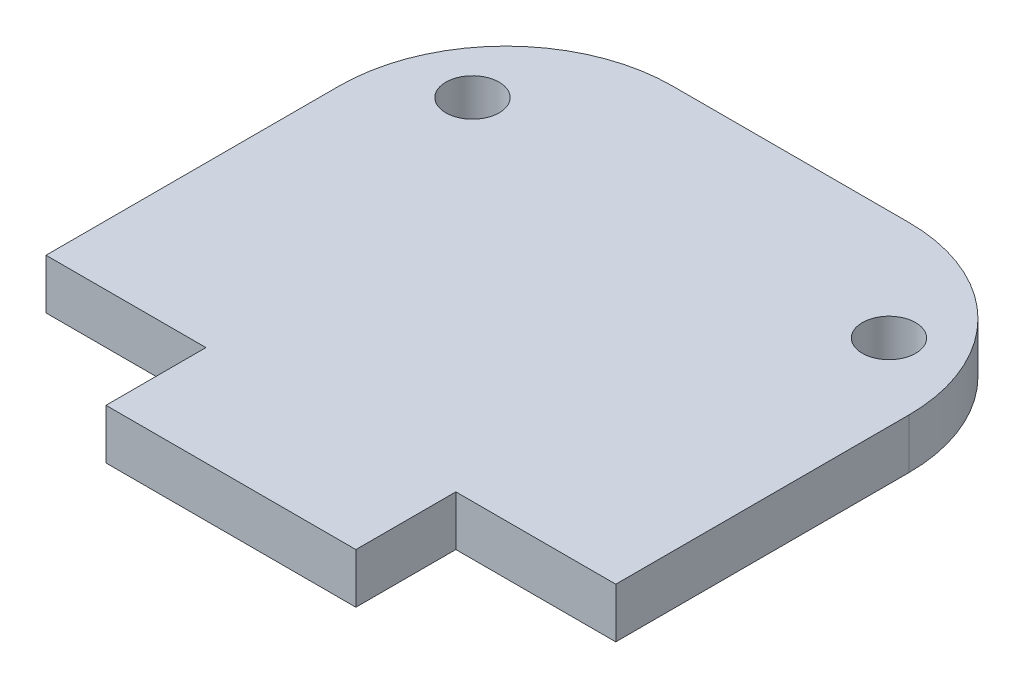
SolidWorks part; units mm, degrees
material "MDF"
ref_plane "Plano frontal" through (0, 0, 0) normal (0, 0, 1) x (1, 0, 0)
ref_plane "Plano superior" through (0, 0, 0) normal (0, 1, 0) x (1, 0, 0)
ref_plane "Plano direito" through (0, 0, 0) normal (1, 0, 0) x (0, 0, -1)
ref_plane "Plano1" through (0, -3, 0) normal (0, -1, 0) x (1, 0, 0)
sketch "Esboço1" plane through (0, -3, 0) normal (0, -1, 0) x (1, 0, 0)
  line L0 (-7.1, -33.6) -> (7.1, -33.6)
  line L1 (17.1, -23.6) -> (17.1, -6)
  line L2 (17.1, -6) -> (7.5, -6)
  line L3 (7.5, -6) -> (7.5, 0)
  line L4 (7.5, 0) -> (-7.5, 0)
  line L5 (-7.5, 0) -> (-7.5, -6)
  line L6 (-7.5, -6) -> (-17.1, -6)
  line L7 (-17.1, -6) -> (-17.1, -23.6)
  line L8 (-12.5, -27) -> (12.5, -27) construction
  line L9 (-7.5, -6) -> (7.5, -6) construction
  arc A0 (7.1, -33.6) -> (17.1, -23.6) centre (7.1, -23.6) ccw
  arc A1 (-17.1, -23.6) -> (-7.1, -33.6) centre (-7.1, -23.6) ccw
  circle A2 centre (-12.5, -27) radius 1.6
  circle A3 centre (12.5, -27) radius 1.6
  point P16 (0, 0)
  point P17 (0, -27)
  point P18 (0, -6)
  dimension "D1" = 25
  dimension "D2" = 3.2
  dimension "D6" = 10
  dimension "D3" = 15
  dimension "D4" = 6
  dimension "D5" = 21
  dimension "D7" = 6.6
  dimension "D8" = 4.6
extrude "Ressalto-extrusão1" add sketch "Esboço1" against normal blind 3
